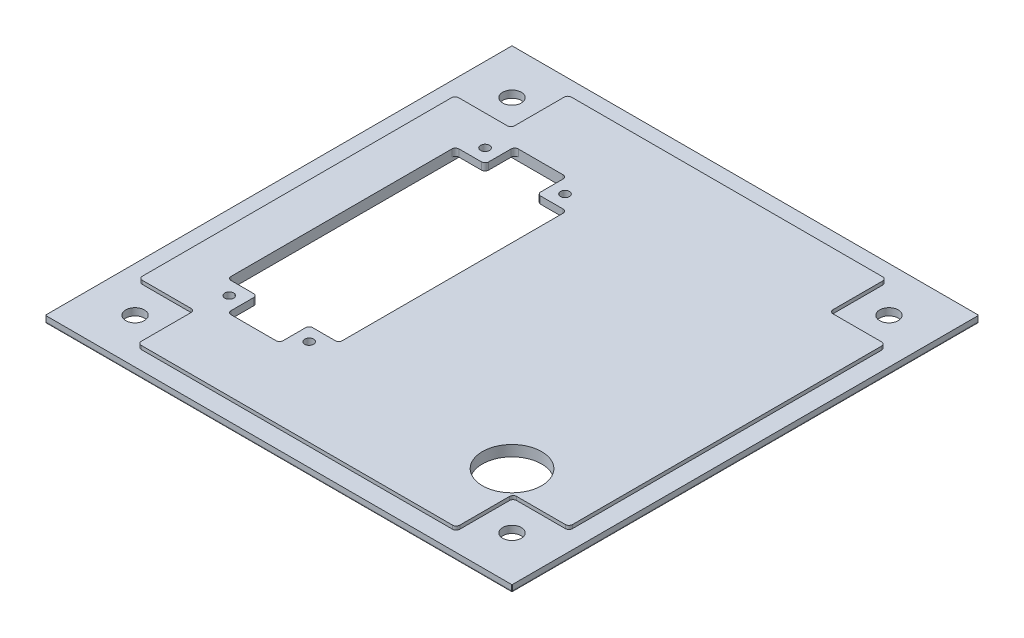
SolidWorks part; units mm, degrees
ref_plane "Front Plane" through (0, 0, 0) normal (0, 0, 1) x (1, 0, 0)
ref_plane "Top Plane" through (0, 0, 0) normal (0, 1, 0) x (1, 0, 0)
ref_plane "Right Plane" through (0, 0, 0) normal (1, 0, 0) x (0, 0, -1)
other "Configuration Table"
sketch "草图1" plane through (0, 0, 0) normal (0, 1, 0) x (1, 0, 0)
  line L1 (-65, 65) -> (65, 65)
  line L2 (-65, 65) -> (-65, -65)
  line L3 (-65, -65) -> (65, -65)
  line L4 (65, 65) -> (65, -65)
  line L5 (-65, 65) -> (65, -65) construction
  line L6 (-65, -65) -> (65, 65) construction
  point P0 (0, 0)
extrude "凸台-拉伸1" add sketch "草图1" along normal blind 3
sketch "草图2" plane through (0, 3, 0) normal (0, 1, 0) x (1, 0, 0)
  line L0 (52.5, 65) -> (52.5, 52.5) construction
  line L1 (65, 65) -> (-65, 65) construction
  line L2 (52.5, 52.5) -> (65, 52.5) construction
  line L3 (65, -65) -> (65, 65) construction
  line L4 (65, 52.5) -> (65, 65) construction
  line L5 (65, 65) -> (52.5, 65) construction
  circle A0 centre (52.5, 52.5) radius 2.6
  circle A1 centre (52.5, -52.5) radius 2.6
  circle A2 centre (-52.5, -52.5) radius 2.6
  circle A3 centre (-52.5, 52.5) radius 2.6
  point P19 (0, 0)
  dimension "D1" = 4
extrude "切除-拉伸1" cut sketch "草图2" against normal through all
sketch "草图4" plane through (0, 3, 0) normal (0, 1, 0) x (1, 0, 0)
  line L0 (65, 65) -> (44.3495, 65)
  line L1 (44.3495, 65) -> (44.3495, 44.0484)
  line L2 (44.3495, 44.0484) -> (65, 44.0484)
  line L3 (65, -65) -> (65, 65) construction
  line L4 (65, 44.0484) -> (65, 65)
  line L9 (-44.3495, -65) -> (-44.3495, -44.0484)
  line L10 (-44.3495, -44.0484) -> (-65, -44.0484)
  line L11 (-65, -44.0484) -> (-65, -65)
  line L12 (-65, -65) -> (-44.3495, -65)
  line L17 (65, -44.3495) -> (44.0484, -44.3495)
  line L18 (44.0484, -44.3495) -> (44.0484, -65)
  line L19 (44.0484, -65) -> (65, -65)
  line L20 (65, -65) -> (65, -44.3495)
  line L21 (-65, 44.3495) -> (-44.0484, 44.3495)
  line L22 (-44.0484, 44.3495) -> (-44.0484, 65)
  line L23 (-44.0484, 65) -> (-65, 65)
  line L24 (-65, 65) -> (-65, 44.3495)
  line L25 (0, 0) -> (0, -65) construction
  line L26 (-65, -65) -> (65, -65) construction
  line L27 (65, -65) -> (44.3495, -65)
  line L28 (65, -44.0484) -> (65, -65)
  line L29 (44.3495, -44.0484) -> (65, -44.0484)
  line L30 (44.3495, -65) -> (44.3495, -44.0484)
  line L31 (-65, 44.0484) -> (-65, 65)
  line L32 (-44.3495, 44.0484) -> (-65, 44.0484)
  line L33 (-44.3495, 65) -> (-44.3495, 44.0484)
  line L34 (-65, 65) -> (-44.3495, 65)
  point P22 (0, 0)
  dimension "D1" = 4
extrude "切除-拉伸2" cut sketch "草图4" against normal blind 1
sketch "草图5" plane through (0, 3, 0) normal (0, 1, 0) x (1, 0, 0)
  line L2 (44.3495, 65) -> (-44.3495, 65) construction
  line L5 (-44.3495, 65) -> (44.3495, 65)
  line L6 (44.3495, 65) -> (44.3495, 59.9)
  line L7 (44.3495, 65) -> (44.3495, 44.0484) construction
  line L8 (-44.3495, 65) -> (-44.3495, 59.9)
  line L9 (65, 44.0484) -> (59.9, 44.0484)
  line L10 (-44.3495, 59.9) -> (44.3495, 59.9)
  line L15 (44.3495, -65) -> (-44.3495, -65)
  line L16 (-44.3495, -65) -> (-44.3495, -59.9)
  line L17 (44.3495, -65) -> (44.3495, -59.9)
  line L18 (44.3495, -59.9) -> (-44.3495, -59.9)
  line L23 (-44.3495, 44.0484) -> (-44.3495, 65) construction
  line L24 (65, 44.3495) -> (65, -44.3495)
  line L25 (65, -44.3495) -> (59.9, -44.3495)
  line L26 (65, 44.3495) -> (59.9, 44.3495)
  line L27 (59.9, 44.3495) -> (59.9, -44.3495)
  line L28 (-65, -44.3495) -> (-65, 44.3495)
  line L29 (-65, 44.3495) -> (-59.9, 44.3495)
  line L30 (-65, -44.3495) -> (-59.9, -44.3495)
  line L31 (-59.9, -44.3495) -> (-59.9, 44.3495)
  line L32 (44.3495, 44.0484) -> (65, 44.0484) construction
  line L33 (65, -44.0484) -> (65, 44.0484) construction
  line L34 (44.3495, 44.0484) -> (65, 44.0484) construction
  line L35 (59.9, 44.0484) -> (59.9, -44.0484)
  line L36 (65, -44.0484) -> (44.3495, -44.0484) construction
  line L37 (59.9, -44.0484) -> (65, -44.0484)
  line L38 (65, -44.0484) -> (65, 44.0484)
  line L39 (0, 0) -> (0, 21.8453) construction
  line L40 (-65, -44.0484) -> (-65, 44.0484)
  line L41 (-59.9, -44.0484) -> (-65, -44.0484)
  line L42 (-59.9, 44.0484) -> (-59.9, -44.0484)
  line L43 (-65, 44.0484) -> (-59.9, 44.0484)
  point P27 (0, 0)
  dimension "D1" = 4
extrude "切除-拉伸3" cut sketch "草图5" against normal up to surface (1 mm away) up to face at (-54.6747, 2, 54.5242)
sketch "草图6" plane through (0, 0, 0) normal (0, -1, 0) x (-1, 0, 0)
  line L0 (60, 65) -> (60, -65) construction
  line L1 (60, 0) -> (47.5, 0) construction
  line L2 (47.5, -35) -> (47.5, 35)
  line L3 (42.5, -40) -> (21.5, -40)
  line L4 (16.5, -35) -> (16.5, 35)
  line L13 (21.5, 40) -> (42.5, 40)
  line L14 (65, -65) -> (-65, -65) construction
  arc A0 (42.5, -40) -> (47.5, -35) centre (42.5, -35) ccw
  arc A1 (21.5, -40) -> (16.5, -35) centre (21.5, -35) cw
  arc A2 (47.5, 35) -> (42.5, 40) centre (42.5, 35) ccw
  arc A3 (16.5, 35) -> (21.5, 40) centre (21.5, 35) cw
  point P9 (47.5, 0)
  dimension "D1" = 5
extrude "切除-拉伸4" cut sketch "草图6" against normal blind 3
sketch "草图7" plane through (0, 3, 0) normal (0, 1, 0) x (1, 0, 0)
  line L8 (-24.75, 40) -> (-24.75, 31.75)
  line L9 (-42.5, 40) -> (-21.5, 40) construction
  line L10 (-24.75, 31.75) -> (-16.5, 31.75)
  line L11 (-16.5, 35) -> (-16.5, -35) construction
  line L12 (-21.5, 40) -> (-24.75, 40)
  line L13 (-16.5, 35) -> (-16.5, 31.75)
  line L14 (-24.75, 31.75) -> (-17.9645, 38.5355) construction
  line L15 (-47.5, 0) -> (-16.5, 0) construction
  line L16 (-47.5, -35) -> (-47.5, 35) construction
  line L17 (-32, 0) -> (-32, 14.0496) construction
  line L18 (-21.5, 40) -> (-24.75, 40)
  line L19 (-16.5, 35) -> (-16.5, 31.75)
  line L20 (-24.75, 31.75) -> (-24.75, 40)
  line L21 (-16.5, 31.75) -> (-24.75, 31.75)
  line L22 (-24.75, 40) -> (-24.75, 31.75)
  line L23 (-24.75, 31.75) -> (-16.5, 31.75)
  line L24 (-21.5, 40) -> (-24.75, 40)
  line L25 (-16.5, 35) -> (-16.5, 31.75)
  line L26 (-21.5, 40) -> (-24.75, 40)
  line L27 (-16.5, 35) -> (-16.5, 31.75)
  line L28 (-24.75, 31.75) -> (-24.75, 40)
  line L29 (-16.5, 31.75) -> (-24.75, 31.75)
  line L30 (-24.75, -31.75) -> (-17.9645, -38.5355) construction
  line L31 (-16.5, -31.75) -> (-24.75, -31.75)
  line L32 (-24.75, -31.75) -> (-24.75, -40)
  line L33 (-16.5, -35) -> (-16.5, -31.75)
  line L34 (-21.5, -40) -> (-24.75, -40)
  line L35 (-16.5, -35) -> (-16.5, -31.75)
  line L36 (-21.5, -40) -> (-24.75, -40)
  line L37 (-24.75, -31.75) -> (-16.5, -31.75)
  line L38 (-24.75, -40) -> (-24.75, -31.75)
  line L39 (-16.5, -31.75) -> (-24.75, -31.75)
  line L40 (-24.75, -31.75) -> (-24.75, -40)
  line L41 (-16.5, -35) -> (-16.5, -31.75)
  line L42 (-21.5, -40) -> (-24.75, -40)
  line L43 (-16.5, -35) -> (-16.5, -31.75)
  line L44 (-21.5, -40) -> (-24.75, -40)
  line L45 (-24.75, -31.75) -> (-16.5, -31.75)
  line L46 (-24.75, -40) -> (-24.75, -31.75)
  line L47 (-39.25, -31.75) -> (-46.0355, -38.5355) construction
  line L48 (-39.25, -40) -> (-39.25, -31.75)
  line L49 (-39.25, -31.75) -> (-47.5, -31.75)
  line L50 (-42.5, -40) -> (-39.25, -40)
  line L51 (-47.5, -35) -> (-47.5, -31.75)
  line L52 (-42.5, -40) -> (-39.25, -40)
  line L53 (-47.5, -35) -> (-47.5, -31.75)
  line L54 (-39.25, -31.75) -> (-39.25, -40)
  line L55 (-47.5, -31.75) -> (-39.25, -31.75)
  line L56 (-39.25, -40) -> (-39.25, -31.75)
  line L57 (-39.25, -31.75) -> (-47.5, -31.75)
  line L58 (-42.5, -40) -> (-39.25, -40)
  line L59 (-47.5, -35) -> (-47.5, -31.75)
  line L60 (-42.5, -40) -> (-39.25, -40)
  line L61 (-47.5, -35) -> (-47.5, -31.75)
  line L62 (-39.25, -31.75) -> (-39.25, -40)
  line L63 (-47.5, -31.75) -> (-39.25, -31.75)
  line L64 (-39.25, 31.75) -> (-46.0355, 38.5355) construction
  line L65 (-47.5, 31.75) -> (-39.25, 31.75)
  line L66 (-39.25, 31.75) -> (-39.25, 40)
  line L67 (-47.5, 35) -> (-47.5, 31.75)
  line L68 (-42.5, 40) -> (-39.25, 40)
  line L69 (-47.5, 35) -> (-47.5, 31.75)
  line L70 (-42.5, 40) -> (-39.25, 40)
  line L71 (-39.25, 31.75) -> (-47.5, 31.75)
  line L72 (-39.25, 40) -> (-39.25, 31.75)
  line L73 (-47.5, 31.75) -> (-39.25, 31.75)
  line L74 (-39.25, 31.75) -> (-39.25, 40)
  line L75 (-47.5, 35) -> (-47.5, 31.75)
  line L76 (-42.5, 40) -> (-39.25, 40)
  line L77 (-47.5, 35) -> (-47.5, 31.75)
  line L78 (-42.5, 40) -> (-39.25, 40)
  line L79 (-39.25, 31.75) -> (-47.5, 31.75)
  line L80 (-39.25, 40) -> (-39.25, 31.75)
  circle A1 centre (-20.8723, 35.6277) radius 1.25
  circle A3 centre (-43.1277, 35.6277) radius 1.25
  arc A6 (-21.5, 40) -> (-16.5, 35) centre (-21.5, 35) cw
  arc A9 (-21.5, -40) -> (-16.5, -35) centre (-21.5, -35) ccw
  arc A10 (-42.5, -40) -> (-47.5, -35) centre (-42.5, -35) cw
  arc A13 (-42.5, 40) -> (-47.5, 35) centre (-42.5, 35) ccw
  circle A14 centre (-20.8723, -35.6277) radius 1.25
  circle A15 centre (-43.1277, -35.6277) radius 1.25
extrude "凸台-拉伸2" add sketch "草图7" against normal blind 2
fillet "圆角1" radius 1 4 edges at (-39.25, 2, 31.75) (-24.75, 2, 31.75) (-39.25, 2, -31.75) (-24.75, 2, -31.75)
sketch "草图15" plane through (0, 0, 0) normal (0, -1, 0) x (-1, 0, 0)
  line L0 (65, -65) -> (-65, -65) construction
  line L4 (-38, -38) -> (-65, -65) construction
  circle A0 centre (-38, -38) radius 8.25
  dimension "D1" = 27
  dimension "D2" = 45
extrude "切除-拉伸9" cut sketch "草图15" against normal through all
chamfer "倒角1" [suppressed] distance 1 angle 45
chamfer "倒角2" distance 0.2 angle 45 4 edges at (-65, 1, -65) (-65, 1, 65) (65, 1, 65) (65, 1, -65)
fillet "圆角2" radius 0.5 4 edges at (0, 0, -65) (-65, 0, 0) (0, 0, 65) (65, 0, 0)
fillet "圆角3" radius 1 12 edges at (-44.3495, 2.5, -59.9) (-44.3495, 2.5, -44.0484) (-59.9, 2.5, -44.0484) (-59.9, 2.5, 44.0484) (-44.3495, 2.5, 44.0484) (-44.3495, 2.5, 59.9) (44.3495, 2.5, 59.9) (44.3495, 2.5, 44.0484) (59.9, 2.5, 44.0484) (59.9, 2.5, -44.0484) (44.3495, 2.5, -44.0484) (44.3495, 2.5, -59.9)
fillet "圆角4" radius 1 8 edges at (-39.25, 2, 40) (-24.75, 2, 40) (-16.5, 2, 31.75) (-16.5, 2, -31.75) (-47.5, 2, 31.75) (-47.5, 2, -31.75) (-39.25, 2, -40) (-24.75, 2, -40)
